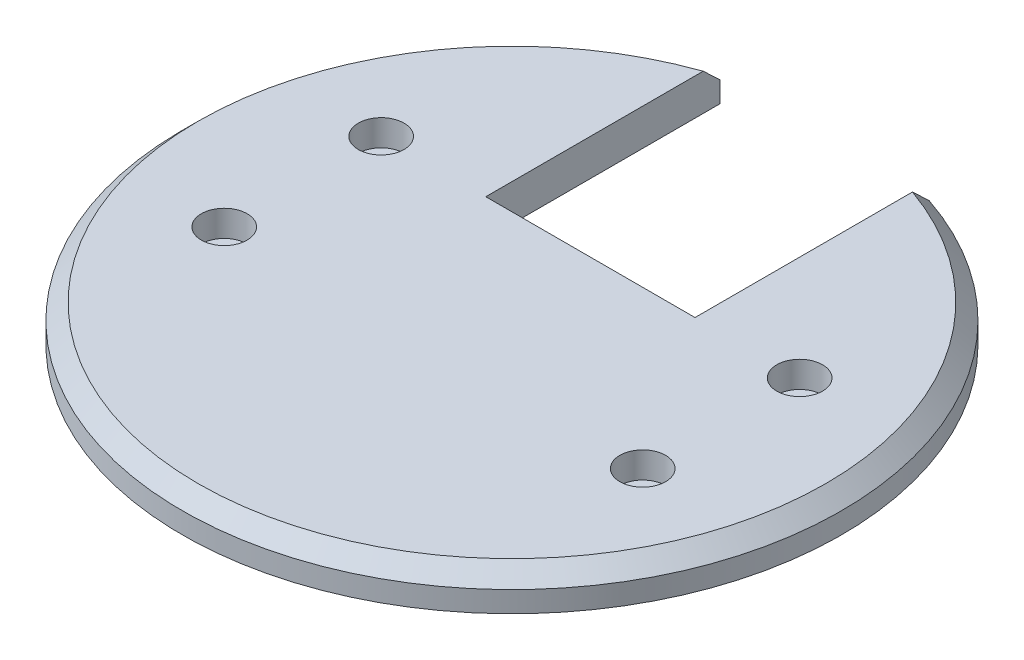
SolidWorks part; units mm, degrees
ref_plane "Front Plane" through (0, 0, 0) normal (0, 0, 1) x (1, 0, 0)
ref_plane "Top Plane" through (0, 0, 0) normal (0, 1, 0) x (1, 0, 0)
ref_plane "Right Plane" through (0, 0, 0) normal (1, 0, 0) x (0, 0, -1)
sketch "Sketch1" plane through (0, 0, 0) normal (0, 1, 0) x (1, 0, 0)
  line L0 (40, 48.6724) -> (40, -48.6724) construction
  line L1 (-40, 48.6724) -> (-40, -48.6724) construction
  line L2 (0, -55) -> (0, 55) construction
  line L3 (-55, 0) -> (55, 0) construction
  circle A0 centre (0, 0) radius 63
  circle A1 centre (-40, 15) radius 2.625
  circle A2 centre (-40, -15) radius 2.625
  circle A3 centre (40, 15) radius 2.625
  circle A4 centre (40, -15) radius 2.625
  dimension "D1" = 126
  dimension "D4" = 5.25
  dimension "D2" = 40
  dimension "D3" = 40
  dimension "D5" = 30
  dimension "D6" = 15
  dimension "D7" = 15
  dimension "D8" = 30
extrude "Boss-Extrude1" add sketch "Sketch1" along normal blind 7
sketch "Sketch2" plane through (0, 7, 0) normal (0, 1, 0) x (1, 0, 0)
  circle A0 centre (-40, 15) radius 4.375
  circle A1 centre (-40, -15) radius 4.375
  circle A2 centre (40, 15) radius 4.375
  circle A3 centre (40, -15) radius 4.375
  dimension "D1" = 8.75
extrude "Cut-Extrude1" cut sketch "Sketch2" against normal blind 5
fillet "Chamfer1" radius 3 1 edges at (0, 7, 63) type face fillet profile chamfer first side face at (-40, 7, 19.375) second side face at (0, 7, 63)
sketch "Sketch3" plane through (0, 7, 0) normal (0, 1, 0) x (1, 0, 0)
  line L0 (0, -3.85) -> (0, 3.85) construction
  line L1 (20, 15) -> (-20, 15)
  line L2 (20, 15) -> (20, 65)
  line L3 (20, 65) -> (-20, 65)
  line L4 (-20, 15) -> (-20, 65)
  line L5 (20, 15) -> (-20, 65) construction
  line L6 (20, 65) -> (-20, 15) construction
  point P0 (0, 40)
  dimension "D1" = 40
  dimension "D2" = 40
  dimension "D3" = 50
extrude "Cut-Extrude2" cut sketch "Sketch3" against normal up to surface (7 mm away) up to face at (0, 0, 63)
